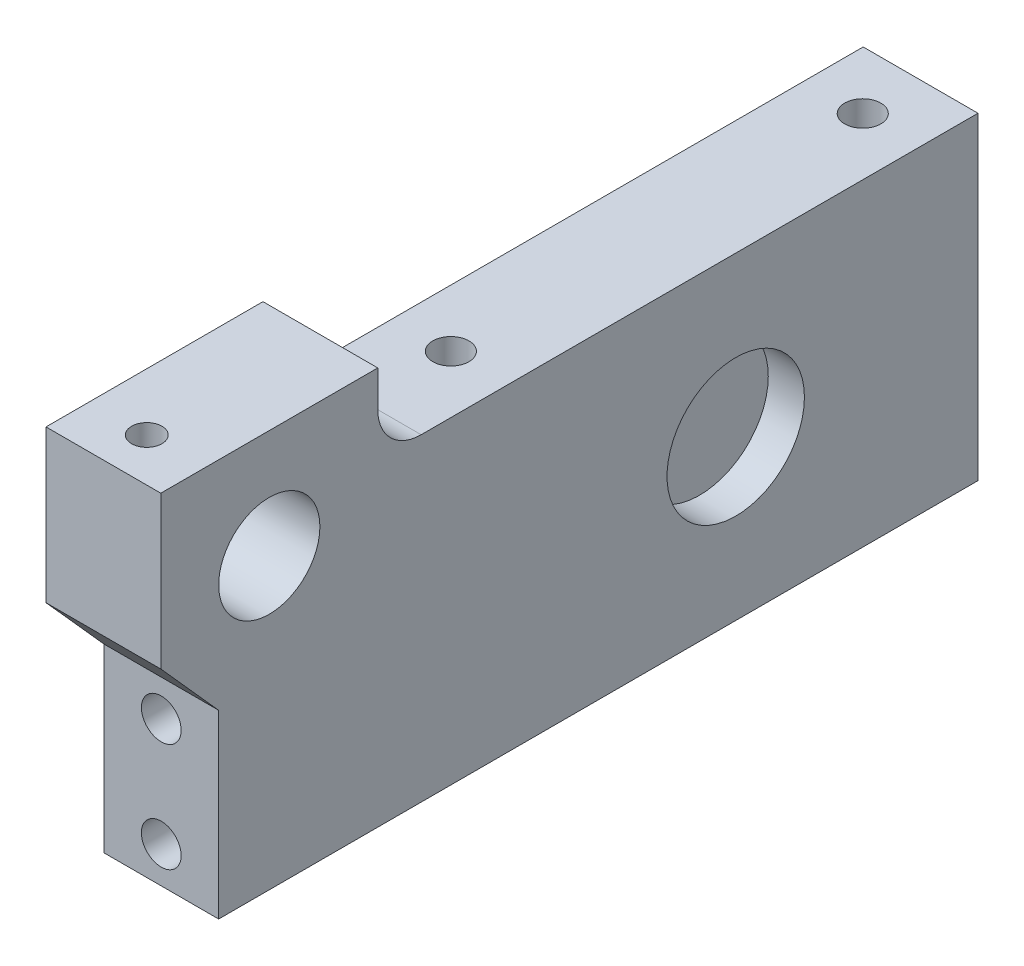
SolidWorks part; units mm, degrees
material "3.0205 (EN-AW 1200)"
ref_plane "Plano frontal" through (0, 0, 0) normal (0, 0, 1) x (1, 0, 0)
ref_plane "Plano superior" through (0, 0, 0) normal (0, 1, 0) x (1, 0, 0)
ref_plane "Plano direito" through (0, 0, 0) normal (1, 0, 0) x (0, 0, -1)
sketch "Esboço1" plane through (0, 0, 0) normal (1, 0, 0) x (0, 0, -1)
  line L0 (-10, 38.5) -> (-40, 38.5)
  line L1 (-10, 27.5) -> (-10, 38.5)
  line L2 (-40, 23.5) -> (-40, 17.4443)
  line L3 (-32, -16.5) -> (73, -16.5)
  line L4 (-32, 8.5) -> (-32, -16.5)
  line L5 (-32, 8.5) -> (-40, 17.4443)
  line L9 (-10, 27.5) -> (73, 27.5)
  line L10 (73, -16.5) -> (73, 27.5)
  line L12 (-40, 23.5) -> (-40, 38.5)
  circle A2 centre (-25, 23.5) radius 7
  dimension "D3" = 14
  dimension "D4" = 44
  dimension "D5" = 15
  dimension "D10" = 15
  dimension "D11" = 25
  dimension "D2" = 83
  dimension "D6" = 40
  dimension "D7" = 15
  dimension "D8" = 25
  dimension "D9" = 23.5
  dimension "D12" = 12
extrude "Ressalto-extrusão1" add sketch "Esboço1" along normal mid plane 15.875 contours L2 L3 | L2 L3 region at (0, 7.1266, -17.5422)
hole_wizard "Escareado para parafuso de máquina com cabeça chata de M51" positions "Esboço2" profile "Esboço3" countersink size "M5" standard "Ansi Metric"
sketch "Esboço2" plane through (33.0625, -10.2517, 40.0704) normal (0, 0, 1) x (1, 0, 0)
  line L0 (0, 0) -> (0, 16.8759) construction
  line L4 (-33.0625, 27.6959) -> (-33.0625, 13.7517) construction
  line L7 (-33.0625, 13.7517) -> (-33.0625, -1.2483) construction
  point P0 (-33.0625, 13.7517)
  point P2 (-33.0625, -1.2483)
  point P29 (33.0625, -1.2483)
  point P30 (33.0625, 13.7517)
sketch "Esboço3" plane through (0, 3.5, 40.0704) normal (1, 0, 0) x (0, -1, 0)
  line L0 (0, 0) -> (0, 31.6524)
  line L1 (0, 31.6524) -> (2.75, 30)
  line L2 (2.75, 30) -> (2.75, 2.45)
  line L3 (2.75, 2.45) -> (5.2, 0)
  line L4 (5.2, 0) -> (0, 0)
  line L5 (-2.75, 2.45) -> (-5.2, 0) construction
  line L6 (0, 31.6524) -> (-2.75, 30) construction
  line L7 (0, -6.35) -> (0, 107.95) construction
  dimension "Hole Dia." = 5.5
  dimension "Hole Depth" = 30
  dimension "Near C'Sink Dia." = 10.4
  dimension "Near C'Sink Angle" = 90
  dimension "Drill Angle" = 118
hole_wizard "Escareado para parafuso de máquina com cabeça chata de M52" positions "Esboço4" profile "Esboço5" countersink size "M6" standard "Ansi Metric"
sketch "Esboço4" plane through (33.0625, -23.5, -11.4602) normal (0, -1, 0) x (-1, 0, 0)
  line L0 (25.125, 61.5398) -> (41, 61.5398) construction
  point P0 (33.06, 53.5398)
  point P2 (33.06, -3.4135)
  point P4 (-33.06, -3.4135)
  point P6 (-33.06, 49.5865)
  dimension "D1" = 8
sketch "Esboço5" plane through (0.0025, -23.5, -65) normal (1, 0, 0) x (0, 0, -1)
  line L0 (0, 0) -> (0, 31.9828)
  line L1 (0, 31.9828) -> (3.3, 30)
  line L2 (3.3, 30) -> (3.3, 3)
  line L3 (3.3, 3) -> (6.3, 0)
  line L4 (6.3, 0) -> (0, 0)
  line L5 (-3.3, 3) -> (-6.3, 0) construction
  line L6 (0, 31.9828) -> (-3.3, 30) construction
  line L7 (0, -6.35) -> (0, 107.95) construction
  dimension "Hole Dia." = 6.6
  dimension "Hole Depth" = 30
  dimension "Near C'Sink Dia." = 12.6
  dimension "Near C'Sink Angle" = 90
  dimension "Drill Angle" = 118
hole_wizard "Broca de rosquear para tarraxa de M5x0.81" positions "Esboço6" profile "Esboço7" hole size "M5x0.8" standard "Ansi Metric"
sketch "Esboço6" plane through (33.0625, 48.5, -11.4602) normal (0, 1, 0) x (1, 0, 0)
  line L0 (41, -45.4602) -> (25.12, -45.4602) construction
  line L3 (-41.005, -45.4602) -> (-25.125, -45.4602) construction
  point P9 (33.06, -45.4602)
  point P20 (-33.065, -45.4602)
sketch "Esboço7" plane through (66.1225, 48.5, 34) normal (1, 0, 0) x (0, 0, 1)
  line L0 (0, 0) -> (0, 21.2618)
  line L1 (0, 21.2618) -> (2.1, 20)
  line L2 (2.1, 20) -> (2.1, 0)
  line L3 (2.1, 0) -> (0, 0)
  line L4 (0, 21.2618) -> (-2.1, 20) construction
  line L5 (0, -6.35) -> (0, 107.95) construction
  dimension "Hole Dia." = 4.2
  dimension "Hole Depth" = 20
  dimension "Drill Angle" = 118
hole_wizard "Broca de rosquear para tarraxa de M5x0.82" positions "Esboço8" profile "Esboço9" hole size "M5x0.8" standard "Ansi Metric"
sketch "Esboço8" plane through (33.0625, -10.2517, 0) normal (0, 0, -1) x (-1, 0, 0)
  line L0 (-33.06, 37.7517) -> (-33.06, 43.7517) construction
  line L3 (33.065, 37.7517) -> (33.065, 43.7517) construction
  point P1 (-33.06, 43.7517)
  point P7 (33.065, 43.7517)
sketch "Esboço9" plane through (66.1225, 33.5, 0) normal (1, 0, 0) x (0, 1, 0)
  line L0 (0, 0) -> (0, 21.2618)
  line L1 (0, 21.2618) -> (2.1, 20)
  line L2 (2.1, 20) -> (2.1, 0)
  line L3 (2.1, 0) -> (0, 0)
  line L4 (0, 21.2618) -> (-2.1, 20) construction
  line L5 (0, -6.35) -> (0, 107.95) construction
  dimension "Hole Dia." = 4.2
  dimension "Hole Depth" = 20
  dimension "Drill Angle" = 118
hole_wizard "Broca de rosquear para tarraxa de M6x1.01" positions "Esboço10" profile "Esboço11" hole size "M6x1.0" standard "Ansi Metric"
sketch "Esboço10" plane through (33.0625, 27.5, -11.4602) normal (0, 1, 0) x (1, 0, 0)
  line L0 (-25.125, 61.5398) -> (-41, 61.5398) construction
  point P0 (33.06, 49.5398)
  point P3 (-33.06, 53.5398)
  point P14 (-33.06, -3.4135)
  point P17 (33.06, -3.4135)
  dimension "D1" = 8
sketch "Esboço11" plane through (66.1225, 27.5, -61) normal (1, 0, 0) x (0, 0, 1)
  line L0 (0, 0) -> (0, 16.5022)
  line L1 (0, 16.5022) -> (2.5, 15)
  line L2 (2.5, 15) -> (2.5, 0)
  line L3 (2.5, 0) -> (0, 0)
  line L4 (0, 16.5022) -> (-2.5, 15) construction
  line L5 (0, -6.35) -> (0, 107.95) construction
  dimension "Hole Dia." = 5
  dimension "Hole Depth" = 15
  dimension "Drill Angle" = 118
fillet "Fillet1" radius 6 1 edges at (0, 27.5, 10)
sketch "Sketch7" plane through (7.9375, 0, 0) normal (1, 0, 0) x (0, 0, -1)
  line L0 (73, -16.5) -> (73, 27.5) construction
  line L1 (-10, 27.5) -> (73, 27.5) construction
  circle A0 centre (39.5, 5.5) radius 9.5
  dimension "D1" = 19
  dimension "D3" = 33.5
  dimension "D4" = 22
extrude "Cut-Extrude4" cut sketch "Sketch7" against normal blind 5
